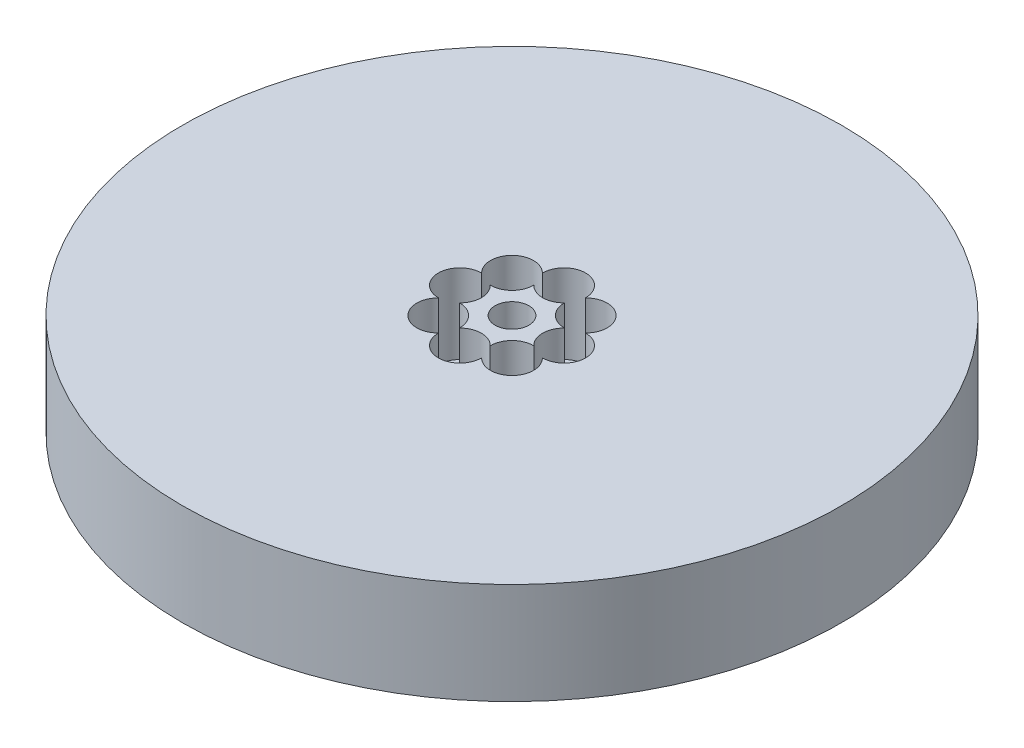
SolidWorks part; units mm, degrees
ref_plane "Front Plane" through (0, 0, 0) normal (0, 0, 1) x (1, 0, 0)
ref_plane "Top Plane" through (0, 0, 0) normal (0, 1, 0) x (1, 0, 0)
ref_plane "Right Plane" through (0, 0, 0) normal (1, 0, 0) x (0, 0, -1)
sketch "Sketch1" plane through (0, 0, 0) normal (0, 1, 0) x (1, 0, 0)
  circle A0 centre (0, 0) radius 97.5
  dimension "FLANGE_OD" = 195
extrude "Boss-Extrude1" add sketch "Sketch1" along normal blind 30
sketch "Sketch2" plane through (0, 0, 0) normal (0, 1, 0) x (1, 0, 0)
  circle A0 centre (0, 0) radius 5
  dimension "BORE_D" = 10
extrude "Cut-Extrude1" cut sketch "Sketch2" along normal through all
sketch "Sketch3" plane through (0, 30, 0) normal (0, 1, 0) x (1, 0, 0)
  circle A0 centre (0, 0) radius 15.4259 construction
  circle A1 centre (-15.4259, 0) radius 6.3577
  dimension "BOLT_D" = 12.7154
  dimension "BOLT_PCD" = 30.8518
extrude "Cut-Extrude2" cut sketch "Sketch3" against normal blind 23.5053
pattern_circular "CirPattern1" count 8 over 360 about axis through (0, 0, 0) along (0, 1, 0) of "Cut-Extrude2"
